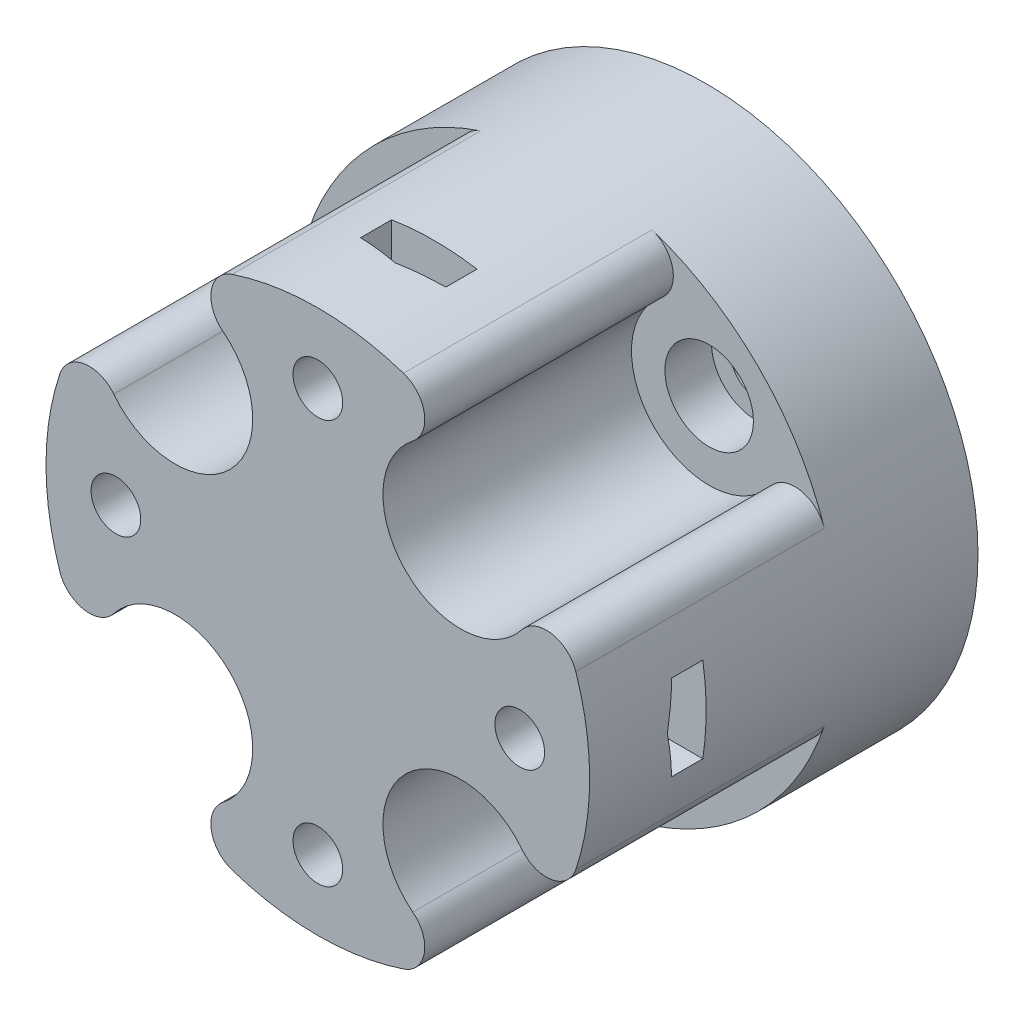
SolidWorks part; units mm, degrees
ref_plane "Front Plane" through (0, 0, 0) normal (1, 0, 0) x (0, 1, 0)
ref_plane "Top Plane" through (0, 0, 0) normal (0, 0, 1) x (0, 1, 0)
ref_plane "Right Plane" through (0, 0, 0) normal (0, 1, 0) x (-1, 0, 0)
sketch "Sketch1" plane through (0, 0, 0) normal (0, 0, 1) x (0, 1, 0)
  line L0 (0, 0) -> (9.1924, 9.1924) construction
  circle A0 centre (0, 0) radius 17.5
  circle A1 centre (0, 0) radius 13 construction
  circle A2 centre (9.1924, 9.1924) radius 1.6
  circle A3 centre (9.1924, 9.1924) radius 2.85
  circle A4 centre (9.1924, -9.1924) radius 2.85
  circle A5 centre (9.1924, -9.1924) radius 1.6
  circle A6 centre (-9.1924, -9.1924) radius 2.85
  circle A7 centre (-9.1924, -9.1924) radius 1.6
  circle A8 centre (-9.1924, 9.1924) radius 2.85
  circle A9 centre (-9.1924, 9.1924) radius 1.6
  point P19 (0, 0)
  dimension "D1" = 35
  dimension "D2" = 26
  dimension "D3" = 3.2
  dimension "D4" = 5.7
  dimension "D5" = 4
extrude "Boss-Extrude1" add sketch "Sketch1" along normal blind 25 contours A0 A8 A6 A4 A3 region at (0, 0, 0)
extrude "Boss-Extrude2" add sketch "Sketch1<3>" along normal blind 6 contours A6 A7 | A8 A9 | A4 A5 | A3 A2 region at (-9.1924, 6.423, 0) region at (9.1924, 6.423, 0) region at (9.1924, -11.9618, 0) region at (-9.1924, -11.9618, 0)
sketch "Sketch1<3>" plane through (0, 0, 0) normal (0, 0, 1) x (0, 1, 0) same geometry as "Sketch1"
sketch "Sketch2" plane through (0, 0, 25) normal (0, 0, 1) x (1, 0, 0)
  circle A0 centre (-9.1924, 9.1924) radius 5
  circle A1 centre (9.1924, 9.1924) radius 5
  circle A2 centre (9.1924, -9.1924) radius 5
  circle A3 centre (-9.1924, -9.1924) radius 5
  dimension "D1" = 10
  dimension "D2" = 2
  dimension "D3" = 2
extrude "Cut-Extrude1" cut sketch "Sketch2" against normal offset from surface (16 mm away) 9 up to face at (17.5, 0, 0)
fillet "Fillet1" radius 2 8 edges at (14.0286, 10.4618, 17) (-14.0286, 10.4618, 17) (-10.4618, 14.0286, 17) (10.4618, 14.0286, 17) (14.0286, -10.4618, 17) (10.4618, -14.0286, 17) (-10.4618, -14.0286, 17) (-14.0286, -10.4618, 17)
sketch "Sketch3" plane through (0, 0, 25) normal (0, 0, 1) x (1, 0, 0)
  line L0 (-2.75, 15.75) -> (-2.75, 17.2826)
  line L2 (-2.75, 15.75) -> (-2.75, 10.25)
  line L3 (-2.75, 10.25) -> (2.75, 10.25)
  line L4 (2.75, 15.75) -> (2.75, 10.25)
  line L5 (-2.75, 15.75) -> (2.75, 10.25) construction
  line L6 (-2.75, 10.25) -> (2.75, 15.75) construction
  line L7 (2.75, 15.75) -> (2.75, 17.2826)
  line L8 (15.75, -2.75) -> (10.25, -2.75)
  line L9 (10.25, 2.75) -> (10.25, -2.75)
  line L10 (15.75, 2.75) -> (10.25, 2.75)
  line L11 (15.75, 2.75) -> (17.2826, 2.75)
  line L12 (15.75, -2.75) -> (17.2826, -2.75)
  line L13 (-2.75, -15.75) -> (-2.75, -10.25)
  line L14 (2.75, -10.25) -> (-2.75, -10.25)
  line L15 (2.75, -15.75) -> (2.75, -10.25)
  line L16 (2.75, -15.75) -> (2.75, -17.2826)
  line L17 (-2.75, -15.75) -> (-2.75, -17.2826)
  line L18 (-15.75, 2.75) -> (-10.25, 2.75)
  line L19 (-10.25, -2.75) -> (-10.25, 2.75)
  line L20 (-15.75, -2.75) -> (-10.25, -2.75)
  line L21 (-15.75, -2.75) -> (-17.2826, -2.75)
  line L22 (-15.75, 2.75) -> (-17.2826, 2.75)
  circle A0 centre (0, 0) radius 13 construction
  circle A2 centre (0, 13) radius 1.6
  arc A3 (5.5152, 16.6082) -> (-5.5152, 16.6082) centre (0, 0) ccw construction
  arc A4 (-2.75, 17.2826) -> (2.75, 17.2826) centre (0, 0) cw
  arc A5 (17.2826, 2.75) -> (17.2826, -2.75) centre (0, 0) cw
  circle A6 centre (13, 0) radius 1.6
  arc A7 (2.75, -17.2826) -> (-2.75, -17.2826) centre (0, 0) cw
  circle A8 centre (0, -13) radius 1.6
  arc A9 (-17.2826, -2.75) -> (-17.2826, 2.75) centre (0, 0) cw
  circle A10 centre (-13, 0) radius 1.6
  point P41 (0, 0)
  dimension "D1" = 26
  dimension "D2" = 3.2
  dimension "D3" = 5.5
  dimension "D4" = 5.5
  dimension "D5" = 4
extrude "Cut-Extrude2" cut sketch "Sketch3" against normal blind 2.5 from offset 5 offset against normal yes
extrude "Cut-Extrude3" cut sketch "Sketch3<2>" against normal blind 10 contours A10 | A2 | A6 | A8 region at (0, 13, 25) region at (13, 0, 25) region at (0, -13, 25) region at (-13, 0, 25)
sketch "Sketch3<2>" plane through (0, 0, 25) normal (0, 0, 1) x (1, 0, 0) same geometry as "Sketch3"
chamfer "Chamfer1" distance 2.75 distance2 0.5 8 edges at (-13.7663, -2.75, 20) (-2.75, 13.7663, 20) (2.75, 13.7663, 20) (13.7663, 2.75, 20) (13.7663, -2.75, 20) (2.75, -13.7663, 20) (-2.75, -13.7663, 20) (-13.7663, 2.75, 20) first distance on face at (-14.6, 0, 20) first distance on face at (-1.6, 13, 20) first distance on face at (11.4, 0, 20) first distance on face at (-1.6, -13, 20)
